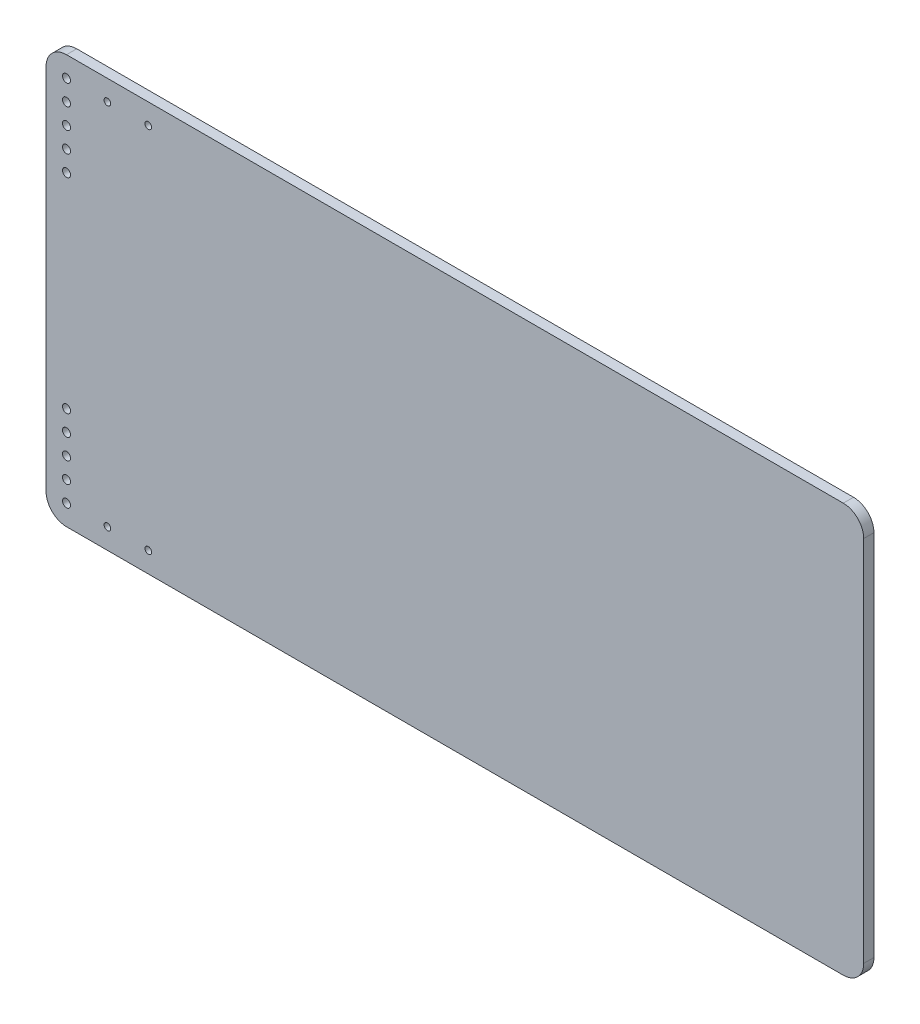
SolidWorks part; units mm, degrees
material "PC High Viscosity"
ref_plane "Front Plane" through (0, 0, 0) normal (0, 0, 1) x (1, 0, 0)
ref_plane "Top Plane" through (0, 0, 0) normal (0, 1, 0) x (1, 0, 0)
ref_plane "Right Plane" through (0, 0, 0) normal (1, 0, 0) x (0, 0, -1)
sketch "Sketch1" plane through (0, 0, 0) normal (0, 0, 1) x (1, 0, 0)
  line L1 (12.7, 0) -> (495.3, 0)
  line L2 (0, 12.7) -> (0, 241.3)
  line L3 (12.7, 254) -> (495.3, 254)
  line L4 (508, 12.7) -> (508, 241.3)
  arc A0 (495.3, 254) -> (508, 241.3) centre (495.3, 241.3) cw
  arc A1 (495.3, 0) -> (508, 12.7) centre (495.3, 12.7) ccw
  arc A2 (12.7, 0) -> (0, 12.7) centre (12.7, 12.7) cw
  arc A3 (0, 241.3) -> (12.7, 254) centre (12.7, 241.3) cw
  point P7 (508, 254)
  point P10 (508, 0)
  point P13 (0, 0)
  point P16 (0, 254)
  dimension "D3" = 12.7
  dimension "D1" = 508
  dimension "D2" = 254
extrude "Boss-Extrude1" add sketch "Sketch1" along normal blind 6.35
sketch "Sketch2" plane through (0, 0, 6.35) normal (0, 0, 1) x (1, 0, 0)
  line L10 (495.3, 254) -> (12.7, 254) construction
  line L11 (0, 241.3) -> (0, 12.7) construction
  line L12 (-20.2403, 127) -> (522.5431, 127) construction
  circle A6 centre (12.7, 190.5) radius 2.5
  circle A7 centre (12.7, 203.2) radius 2.5
  circle A8 centre (12.7, 215.9) radius 2.5
  circle A9 centre (12.7, 228.6) radius 2.5
  circle A10 centre (12.7, 241.3) radius 2.4892
  circle A11 centre (38.1, 241.3) radius 2.0701
  circle A12 centre (63.5, 241.3) radius 2.0701
  circle A13 centre (63.5, 12.7) radius 2.0701
  circle A14 centre (38.1, 12.7) radius 2.0701
  circle A15 centre (12.7, 63.5) radius 2.5
  circle A16 centre (12.7, 50.8) radius 2.5
  circle A17 centre (12.7, 38.1) radius 2.5
  circle A18 centre (12.7, 25.4) radius 2.5
  circle A19 centre (12.7, 12.7) radius 2.4892
  point P1 (522.5431, 116.0338)
  point P10 (-33.4588, 127)
  point P11 (-20.2403, 127)
  dimension "D2" = 12.7
  dimension "D3" = 5
  dimension "D4" = 4.1402
  dimension "D5" = 4.1402
  dimension "D6" = 4.9784
  dimension "D7" = 5
  dimension "D8" = 5
  dimension "D9" = 5
  dimension "D10" = 12.7
  dimension "D11" = 127
  dimension "D12" = 25.4
  dimension "D13" = 25.4
  dimension "D14" = 12.7
  dimension "D15" = 12.7
  dimension "D16" = 12.7
  dimension "D17" = 12.7
extrude "Cut-Extrude1" cut sketch "Sketch2" against normal through all
